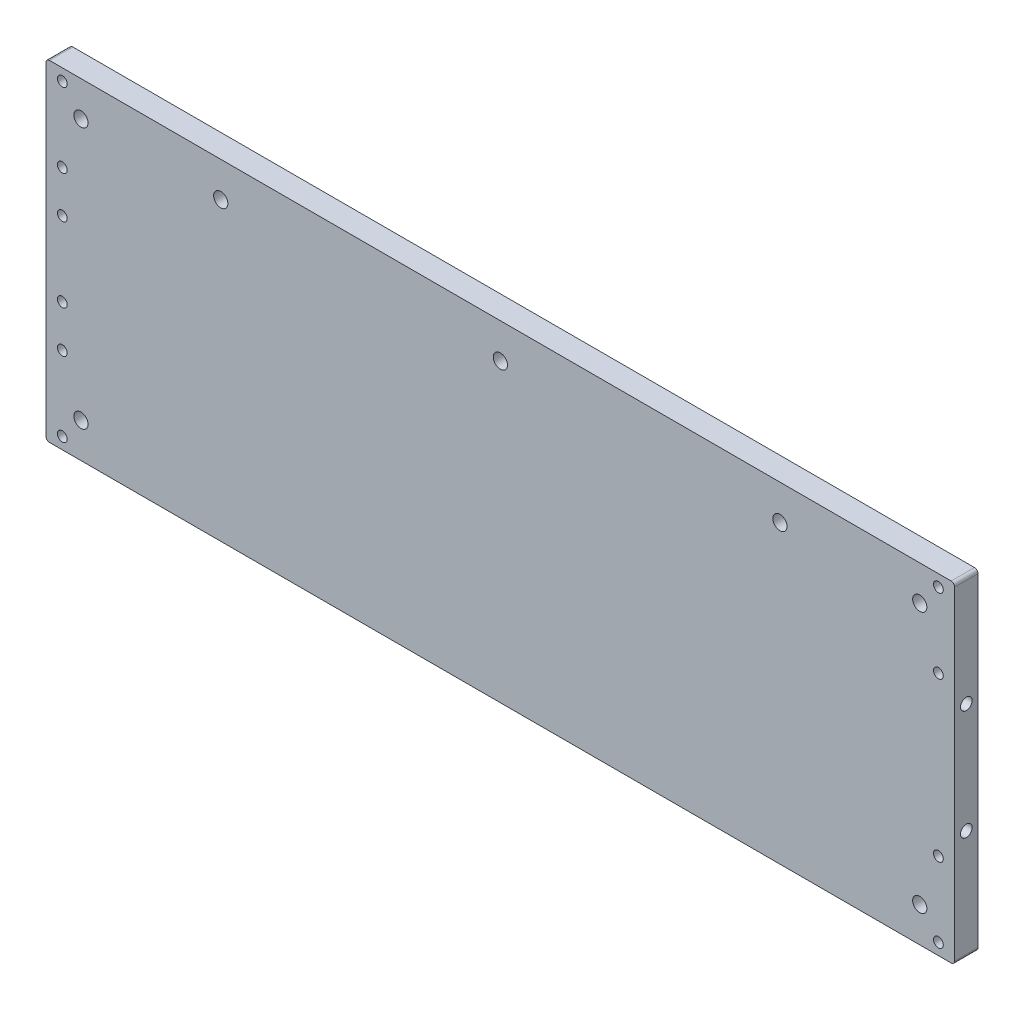
SolidWorks part; units mm, degrees
ref_plane "Front Plane" through (0, 0, 0) normal (0, 0, 1) x (1, 0, 0)
ref_plane "Top Plane" through (0, 0, 0) normal (0, 1, 0) x (1, 0, 0)
ref_plane "Right Plane" through (0, 0, 0) normal (1, 0, 0) x (0, 0, -1)
sketch "Sketch1" plane through (0, 0, 0) normal (0, 0, 1) x (1, 0, 0)
  line L1 (195, -71) -> (-195, -71)
  line L2 (195, -71) -> (195, 71)
  line L3 (195, 71) -> (-195, 71)
  line L4 (-195, -71) -> (-195, 71)
  line L5 (195, -71) -> (-195, 71) construction
  line L6 (195, 71) -> (-195, -71) construction
  point P0 (0, 0)
  dimension "D1" = 390
  dimension "D2" = 142
extrude "Boss-Extrude1" add sketch "Sketch1" along normal mid plane 10
sketch "Sketch2" plane through (0, 0, -5) normal (0, 0, -1) x (-1, 0, 0)
  line L0 (-188, 71) -> (-188, -71) construction
  line L1 (-195, 71) -> (195, 71) construction
  line L2 (195, -71) -> (-195, -71) construction
  line L3 (-195, -71) -> (-195, 71) construction
  line L4 (188, 71) -> (188, -71) construction
  line L5 (195, 71) -> (195, -71) construction
  line L6 (-195, 66) -> (195, 66) construction
  line L7 (-195, -66) -> (195, -66) construction
  line L8 (-195, 34) -> (195, 34) construction
  line L9 (-195, -34) -> (195, -34) construction
  circle A0 centre (-188, 66) radius 2.1
  circle A1 centre (-188, -66) radius 2.1
  circle A2 centre (188, 66) radius 2.1
  circle A3 centre (188, -66) radius 2.1
  circle A4 centre (-188, 34) radius 2.1
  circle A5 centre (-188, -34) radius 2.1
  circle A6 centre (188, 34) radius 2.1
  circle A7 centre (188, -34) radius 2.1
  dimension "D5" = 4.2
  dimension "D6" = 4.2
  dimension "D7" = 4.2
  dimension "D8" = 4.2
  dimension "D11" = 4.2
  dimension "D12" = 4.2
  dimension "D13" = 4.2
  dimension "D14" = 4.2
  dimension "D1" = 7
  dimension "D2" = 7
  dimension "D3" = 5
  dimension "D4" = 5
  dimension "D9" = 32
  dimension "D10" = 32
extrude "Cut-Extrude1" cut sketch "Sketch2" against normal through all
sketch "Sketch3" plane through (0, 0, 5) normal (0, 0, 1) x (1, 0, 0)
  line L0 (-195, 56) -> (195, 56) construction
  line L1 (-195, 71) -> (-195, -71) construction
  line L2 (195, -71) -> (195, 71) construction
  line L3 (-195, -56) -> (195, -56) construction
  line L4 (-180, 71) -> (-180, -71) construction
  line L5 (195, 71) -> (-195, 71) construction
  line L6 (-195, -71) -> (195, -71) construction
  line L7 (180, 71) -> (180, -71) construction
  line L8 (-120, 71) -> (-120, -71) construction
  line L9 (120, 71) -> (120, -71) construction
  circle A0 centre (-180, 56) radius 3.05
  circle A1 centre (180, 56) radius 3.05
  circle A2 centre (180, -56) radius 3.05
  circle A3 centre (-180, -56) radius 3.05
  circle A4 centre (0, 56) radius 3.05
  circle A5 centre (-120, 56) radius 3.05
  circle A6 centre (120, 56) radius 3.05
  dimension "D5" = 6.1
  dimension "D6" = 6.1
  dimension "D7" = 6.1
  dimension "D8" = 6.1
  dimension "D9" = 6.1
  dimension "D12" = 6.1
  dimension "D13" = 6.1
  dimension "D1" = 15
  dimension "D2" = 15
  dimension "D3" = 15
  dimension "D4" = 15
  dimension "D10" = 75
  dimension "D11" = 75
extrude "Cut-Extrude2" cut sketch "Sketch3" against normal through all
sketch "Sketch4" plane through (0, 0, 5) normal (0, 0, 1) x (1, 0, 0)
  circle A0 centre (-180, 56) radius 5
  circle A1 centre (-180, -56) radius 5
  circle A2 centre (180, 56) radius 5
  circle A3 centre (180, -56) radius 5
  dimension "D1" = 10
  dimension "D2" = 10
  dimension "D3" = 10
  dimension "D4" = 10
extrude "Cut-Extrude3" [suppressed] cut sketch "Sketch4" against normal blind 3.5
sketch "Sketch5" plane through (195, 0, 0) normal (1, 0, 0) x (0, 0, -1)
  line L0 (0, 71) -> (0, -71) construction
  line L1 (-5, 71) -> (5, 71) construction
  line L2 (-5, -71) -> (5, -71) construction
  circle A0 centre (0, 23.6) radius 2.5
  circle A1 centre (0, -23.6) radius 2.5
  dimension "D1" = 5
  dimension "D2" = 5
  dimension "D3" = 23.6
  dimension "D4" = 23.6
extrude "Cut-Extrude4" cut sketch "Sketch5" against normal blind 10
sketch "Sketch6" plane through (0, 0, 5) normal (0, 0, 1) x (1, 0, 0)
  line L0 (-188, 34) -> (-188, -34) construction
  line L1 (-188, 0) -> (195, 0) construction
  line L2 (195, -71) -> (195, 71) construction
  circle A0 centre (-188, 16) radius 2.1
  circle A1 centre (-188, -16) radius 2.1
  circle A2 centre (-188, 34) radius 2.1 construction
  dimension "D1" = 16
  dimension "D3" = 4.2
  dimension "D4" = 4.2
  dimension "D2" = 16
extrude "Cut-Extrude5" cut sketch "Sketch6" against normal through all
fillet "Fillet1" radius 1.5 4 edges at (-195, -71, 0) (195, -71, 0) (195, 71, 0) (-195, 71, 0)
equation "\"D3@Sketch5\"=47.2/2"
equation "\"D4@Sketch5\"=47.2/2"
equation "\"D1@Sketch6\"=32/2"
equation "\"D2@Sketch6\"=32/2"
equation "\"D6@Sketch3\"=6.1"
equation "\"D13@Sketch3\"=\"D6@Sketch3\""
equation "\"D9@Sketch3\"=\"D6@Sketch3\""
equation "\"D12@Sketch3\"=\"D6@Sketch3\""
equation "\"D7@Sketch3\"=\"D6@Sketch3\""
equation "\"D5@Sketch3\"=\"D6@Sketch3\""
equation "\"D8@Sketch3\"=\"D6@Sketch3\""
equation "\"D14@Sketch2\"=\"D7@Sketch2\""
equation "\"D13@Sketch2\"=\"D7@Sketch2\""
equation "\"D8@Sketch2\"=\"D7@Sketch2\""
equation "\"D5@Sketch2\"=\"D7@Sketch2\""
equation "\"D11@Sketch2\"=\"D7@Sketch2\""
equation "\"D12@Sketch2\"=\"D7@Sketch2\""
equation "\"D6@Sketch2\"=\"D7@Sketch2\""
equation "\"D3@Sketch6\"=\"D4@Sketch6\""
